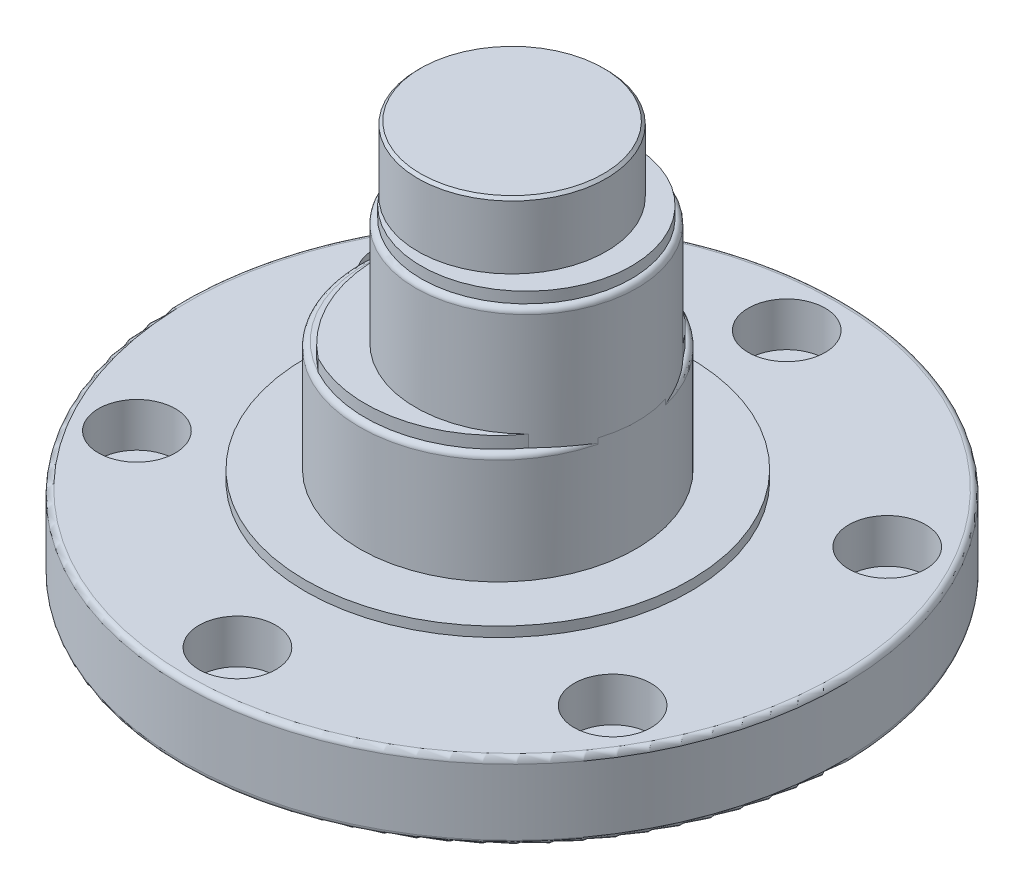
SolidWorks part; units mm, degrees
ref_plane "Front Plane" through (0, 0, 0) normal (0, 0, 1) x (1, 0, 0)
ref_plane "Top Plane" through (0, 0, 0) normal (0, 1, 0) x (1, 0, 0)
ref_plane "Right Plane" through (0, 0, 0) normal (1, 0, 0) x (0, 0, -1)
sketch "Sketch1" plane through (0, 0, 0) normal (0, 1, 0) x (1, 0, 0)
  circle A0 centre (0, 0) radius 25 construction
  circle A1 centre (0, 0) radius 30
  circle A2 centre (0, 25) radius 2.05
  circle A3 centre (21.6506, 12.5) radius 2.05
  circle A4 centre (21.6506, -12.5) radius 2.05
  circle A5 centre (0, -25) radius 2.05
  circle A6 centre (-21.6506, -12.5) radius 2.05
  circle A7 centre (-21.6506, 12.5) radius 2.05
  point P18 (0, 0)
  dimension "D1" = 50
  dimension "D2" = 60
  dimension "D3" = 4.1
  dimension "D4" = 6
extrude "Boss-Extrude1" add sketch "Sketch1" along normal blind 7
sketch "Sketch2" plane through (0, 7, 0) normal (0, 1, 0) x (1, 0, 0)
  circle A0 centre (-1.3, 0) radius 12.575
  point P0 (0, 0)
  point P1 (-1.3, 0)
  dimension "D2" = 25.15
  dimension "D1" = 1.3
extrude "Boss-Extrude2" add sketch "Sketch2" along normal blind 11
sketch "Sketch3" plane through (0, 18, 0) normal (0, 1, 0) x (1, 0, 0)
  circle A0 centre (1.3, 0) radius 10.075
  point P0 (1.3, 0)
  dimension "D2" = 20.15
  dimension "D1" = 1.3
extrude "Boss-Extrude3" add sketch "Sketch3" along normal blind 11
fillet "Fillet1" radius 0.5 4 edges at (1.3, 29, 10.075) (-13.875, 18, 0) (0, 0, 30) (0, 7, 30)
sketch "Sketch4" plane through (0, 7, 0) normal (0, 1, 0) x (1, 0, 0)
  circle A0 centre (0, 25) radius 3.5
  circle A1 centre (21.6506, 12.5) radius 3.5
  circle A2 centre (21.6506, -12.5) radius 3.5
  circle A3 centre (0, -25) radius 3.5
  circle A4 centre (-21.6506, -12.5) radius 3.5
  circle A5 centre (-21.6506, 12.5) radius 3.5
  point P16 (0, 0)
  dimension "D1" = 7
  dimension "D2" = 6
extrude "Cut-Extrude1" cut sketch "Sketch4" against normal blind 4
sketch "Sketch5" plane through (0, 29, 0) normal (0, 1, 0) x (1, 0, 0)
  circle A0 centre (0, 0) radius 8.575
  dimension "D1" = 17.15
extrude "Boss-Extrude4" add sketch "Sketch5" along normal blind 7
sketch "Sketch6" plane through (0, 7, 0) normal (0, 1, 0) x (1, 0, 0)
  circle A0 centre (-1.3, 0) radius 12.575 construction
  circle A1 centre (-1.3, 0) radius 12.575
  circle A2 centre (-1.3, 0) radius 17.5
  dimension "D1" = 35
extrude "Boss-Extrude5" add sketch "Sketch6" along normal blind 0.9
sketch "Sketch7" plane through (0, 18, 0) normal (0, 1, 0) x (1, 0, 0)
  circle A0 centre (1.3, 0) radius 10.075 construction
  circle A1 centre (1.3, 0) radius 10.075
  arc A3 (8.5192, 7.0277) -> (8.5192, -7.0277) centre (-1.3, 0) ccw construction
  arc A4 (8.5192, 7.0277) -> (-7.0085, 10.6404) centre (-1.3, 0) ccw
  arc A5 (-7.0085, 10.6404) -> (-7.0085, -10.6404) centre (1.3, 0) ccw
  arc A6 (-7.0085, -10.6404) -> (8.5192, -7.0277) centre (-1.3, 0) ccw
  arc M2 (8.5192, -7.0277) -> (8.5192, 7.0277) centre (1.3, 0) cw
  arc M3 (8.5192, 7.0277) -> (8.5192, -7.0277) centre (-1.3, 0) ccw
  dimension "D1" = 13.5
extrude "Boss-Extrude6" add sketch "Sketch7" along normal blind 1.1 contours A5 M3 M2 region at (-9.0932, 18, 0)
chamfer "Chamfer1" distance 0.25 angle 45 1 edges at (0, 36, 8.575)
sketch "Sketch8" plane through (0, 29, 0) normal (0, 1, 0) x (1, 0, 0)
  circle A0 centre (0, 0) radius 8.575 construction
  arc A1 (-6.3308, -5.7838) -> (-6.3308, 5.7838) centre (1.3, 0) ccw construction
  circle A2 centre (0, 0) radius 8.575
  arc A3 (-6.3308, -5.7838) -> (-6.3308, 5.7838) centre (1.3, 0) ccw
  arc M1 (-6.3308, -5.7838) -> (-6.3308, 5.7838) centre (1.3, 0) ccw
  arc M2 (-6.3308, 5.7838) -> (-6.3308, -5.7838) centre (0, 0) cw
extrude "Boss-Extrude7" add sketch "Sketch8" along normal blind 1 contours M2 M1 region at (3.1951, 29, -8.2343)
